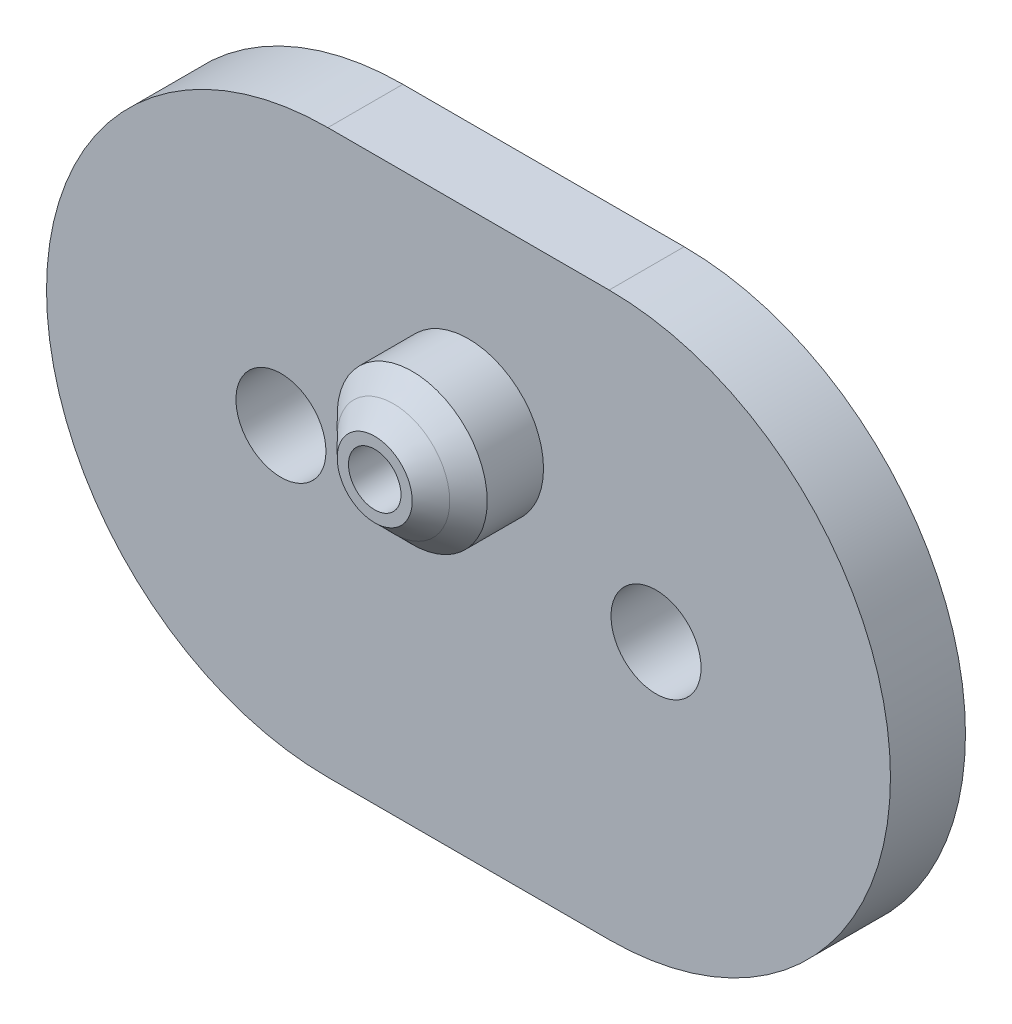
SolidWorks part; units mm, degrees
ref_plane "前视基准面" through (0, 0, 0) normal (0, 0, 1) x (1, 0, 0)
ref_plane "上视基准面" through (0, 0, 0) normal (0, 1, 0) x (1, 0, 0)
ref_plane "右视基准面" through (0, 0, 0) normal (1, 0, 0) x (0, 0, -1)
sketch "草图1" plane through (0, 0, 0) normal (0, 0, 1) x (1, 0, 0)
  line L0 (-7.5, 0) -> (7.5, 0) construction
  line L1 (-7.5, 15) -> (7.5, 15)
  line L2 (-7.5, -15) -> (7.5, -15)
  arc A0 (-7.5, 15) -> (-7.5, -15) centre (-7.5, 0) ccw
  arc A1 (7.5, -15) -> (7.5, 15) centre (7.5, 0) ccw
  circle A2 centre (0, 5) radius 1.4
  circle A3 centre (-10, 0) radius 2.4
  circle A4 centre (10, 0) radius 2.4
  circle A5 centre (0, 5) radius 4
  circle A6 centre (0, 5) radius 2
  point P3 (0, 0)
  dimension "D1" = 15
  dimension "D3" = 2.8
  dimension "D4" = 5
  dimension "D5" = 4.8
  dimension "D6" = 10
  dimension "D7" = 10
  dimension "D8" = 4
  dimension "D9" = 8
  dimension "D2" = 15
extrude "凸台-拉伸1" add sketch "草图1" along normal blind 4 contours L2 A1 L1 A0 A5 A4 A3 region at (0, -0.2348, 0)
extrude "凸台-拉伸2" add sketch "草图1<3>" along normal blind 8 contours A5 A2 region at (-3.8869, 5, 0)
sketch "草图1<3>" plane through (0, 0, 0) normal (0, 0, 1) x (1, 0, 0) same geometry as "草图1"
extrude "凸台-拉伸3" add sketch "草图1<4>" along normal blind 9 contours A6 A2 region at (-1.9434, 5, 0)
sketch "草图1<4>" plane through (0, 0, 0) normal (0, 0, 1) x (1, 0, 0) same geometry as "草图1"
chamfer "倒角1" distance 1 angle 45 2 edges at (2, 5, 8) (4, 5, 8)
